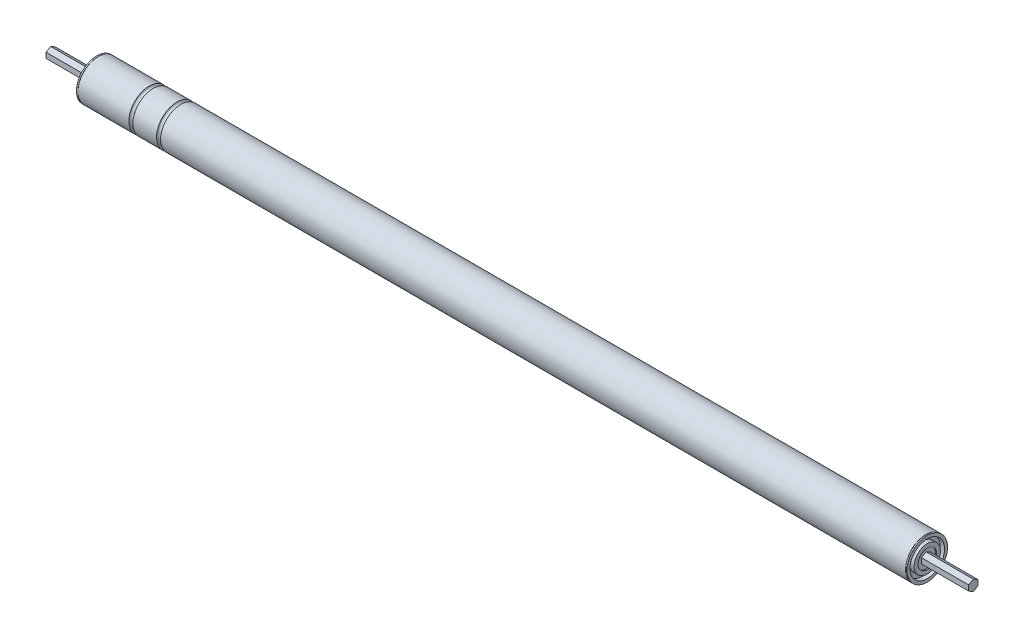
SolidWorks part; units mm, degrees
ref_plane "Front Plane" through (0, 0, 0) normal (0, 0, 1) x (1, 0, 0)
ref_plane "Top Plane" through (0, 0, 0) normal (0, 1, 0) x (1, 0, 0)
ref_plane "Right Plane" through (0, 0, 0) normal (1, 0, 0) x (0, 0, -1)
sketch "Sketch1" plane through (0, 0, 0) normal (0, 0, 1) x (1, 0, 0)
  line L0 (-493.7125, 0) -> (493.7125, 0) construction
  line L1 (493.7125, 0) -> (508, 0) construction
  line L2 (-493.7125, 0) -> (-508, 0) construction
  line L3 (0, 24.13) -> (0, -24.13) construction
  line L4 (-508, 5.5562) -> (-508, -5.5563) construction
  line L5 (508, 5.5562) -> (508, -5.5562) construction
  line L6 (-495.0969, 24.13) -> (-495.0969, -24.13) construction
  line L7 (-495.0969, 0) -> (495.0969, 0) construction
  line L8 (495.0969, 24.13) -> (495.0969, -24.13) construction
  line L9 (-430.2125, 24.13) -> (-430.2125, -24.13) construction
  line L10 (-432.5937, 21.7188) -> (-427.8312, 21.7188) construction
  line L11 (-495.3, 11.1125) -> (-495.3, -11.1125) construction
  line L12 (495.3, 11.1125) -> (495.3, -11.1125) construction
  point P2 (-495.3, 0)
  point P6 (495.3, 0)
  point P23 (-430.2125, 21.7188)
  dimension "D1" = 1.5875
  dimension "D2" = 1.5875
  dimension "BF" = 990.6
  dimension "Overall Width" = 1016
  dimension "D4" = 48.26
  dimension "D5" = 11.1125
  dimension "D6" = 990.1937
  dimension "D8" = 2.4112
  dimension "D9" = 4.7625
  dimension "D10" = 22.225
  dimension "Bearing to Groove Width" = 63.5
sketch "Sketch2" plane through (0, 0, 0) normal (0, 0, 1) x (1, 0, 0)
  line L0 (-493.7125, 0) -> (-493.7125, 11.1125)
  line L1 (-493.7125, 11.1125) -> (-495.0969, 11.1125)
  line L2 (-495.0969, 24.13) -> (-495.0969, -24.13) construction
  line L3 (-493.7125, 0) -> (-508, 0) construction
  line L4 (-495.0969, 11.1125) -> (-495.0969, 15.7129)
  line L5 (-493.7125, 0) -> (-487.9849, 0) construction
  line L6 (-493.7125, 0) -> (-487.9849, 0)
  line L7 (-495.0969, 15.7129) -> (-489.7629, 15.7129)
  line L8 (-489.7629, 15.7129) -> (-489.7629, 20.574)
  line L9 (-495.0969, 24.13) -> (-495.0969, 20.574)
  line L10 (-495.0969, 20.574) -> (-489.7629, 20.574)
  line L11 (-495.0969, 24.13) -> (-493.3189, 24.13)
  line L12 (-493.3189, 24.13) -> (-493.3189, 22.352)
  line L13 (-493.3189, 22.352) -> (-487.9849, 22.352)
  line L14 (-487.9849, 22.352) -> (-487.9849, 0)
  line L15 (-493.7125, 0) -> (493.7125, 0) construction
  line L16 (-508, 5.5562) -> (-508, -5.5563) construction
  dimension "D3" = 22.225
  dimension "D1" = 1.778
  dimension "D2" = 1.778
  dimension "D4" = 1.778
  dimension "D5" = 31.4259
  dimension "D6" = 1.778
  dimension "D7" = 5.334
revolve "Revolve1" add sketch "Sketch2" angle 360 mid plane about L5
mirror "Mirror2" about plane through (0, 0, 0) normal (1, 0, 0) of bodies 101
sketch "Sketch3" plane through (0, 0, 0) normal (1, 0, 0) x (0, 0, -1)
  circle A0 centre (0, 0) radius 24.13
  circle A1 centre (0, 0) radius 22.352 construction
  circle A2 centre (0, 0) radius 22.352 construction
extrude "Boss-Extrude1" add sketch "Sketch3" along normal up to surface (487.9849 mm away) and the other way up to surface (487.9849 mm away) up to face at (487.9849, -22.352, 0) other way up to face at (-487.9849, -22.352, 0)
chamfer "Chamfer1" distance 0.254 angle 45 2 edges at (-493.3189, -24.13, 0) (493.3189, -24.13, 0)
sketch "Sketch6" plane through (-487.9849, 0, 0) normal (-1, 0, 0) x (0, 0, 1)
  circle A0 centre (0, 0) radius 22.352 construction
  circle A1 centre (0, 0) radius 24.13
  circle A2 centre (0, 0) radius 24.13
  circle A3 centre (0, 0) radius 22.352
  dimension "D1" = 0
extrude "Boss-Extrude3" add sketch "Sketch6" along normal up to surface and the other way up to surface up to face at (-493.3189, -23.876, 0) other way up to face at (493.3189, 23.876, 0)
sketch "Sketch4" plane through (0, 0, 0) normal (1, 0, 0) x (0, 0, -1)
  line L1 (0, 6.4158) -> (-5.5563, 3.2079)
  line L2 (-5.5563, 3.2079) -> (-5.5563, -3.2079)
  line L3 (-5.5563, -3.2079) -> (0, -6.4158)
  line L4 (0, -6.4158) -> (5.5562, -3.2079)
  line L5 (5.5562, -3.2079) -> (5.5562, 3.2079)
  line L6 (5.5562, 3.2079) -> (0, 6.4158)
  circle A0 centre (0, 0) radius 5.5563 construction
  point P1 (5.5562, -3.2079)
  point P10 (5.5562, 0)
  dimension "D1" = 11.1125
extrude "Boss-Extrude2" add sketch "Sketch4" along normal up to vertex and the other way up to vertex up to point (508, 0, 0) other way up to point (-508, 0, 0)
sketch "Sketch5" plane through (0, 0, 0) normal (0, 0, 1) x (1, 0, 0)
  line L0 (-432.5937, 21.7188) -> (-427.8312, 21.7188) construction
  line L1 (-430.2125, 24.13) -> (-430.2125, -24.13) construction
  line L2 (-432.5937, 21.7188) -> (-432.5937, 25.5224) construction
  line L3 (-508, 0) -> (-493.7125, 0) construction
  line L7 (-430.2125, 24.1) -> (-432.5937, 24.1) construction
  line L8 (-433.3811, 24.8874) -> (-433.3811, 25.5224)
  line L9 (-433.3811, 25.5224) -> (-427.0439, 25.5224)
  line L10 (-427.0439, 24.8874) -> (-427.0439, 25.5224)
  arc A0 (-432.5937, 24.1) -> (-427.8313, 24.1) centre (-430.2125, 24.1) ccw
  arc A1 (-427.8313, 24.1) -> (-427.0439, 24.8874) centre (-427.0439, 24.1) cw
  arc A2 (-432.5937, 24.1) -> (-433.3811, 24.8874) centre (-433.3811, 24.1) ccw
  dimension "D2" = 0.7874
  dimension "D1" = 0.03
  dimension "D3" = 0.635
revolve "Cut-Revolve1" cut sketch "Sketch5" angle 360 mid plane about L3
pattern_linear "LPattern1" count 2 spacing 33.02 along (1, 0, 0) of "Cut-Revolve1"
ref_axis "Center Axis 1" through (307.34, 0, 0) along (-1, 0, 0)
ref_plane "Contact Plane 1" through (-508, 0, 0) normal (-1, 0, 0) x (0, 0, 1)
ref_plane "Contact Plane 2" through (-493.7125, 0, 0) normal (-1, 0, 0) x (0, 0, 1)
extrude "Boss-Extrude4" add sketch "Sketch4<2>" along normal blind 550
sketch "Sketch4<2>" plane through (0, 0, 0) normal (1, 0, 0) x (0, 0, -1) same geometry as "Sketch4"
extrude "Boss-Extrude5" add sketch "Sketch4<3>" against normal blind 550
sketch "Sketch4<3>" plane through (0, 0, 0) normal (1, 0, 0) x (0, 0, -1) same geometry as "Sketch4"
equation "\"D6@Sketch1\" = \"BF@Sketch1\"-.40625"
equation "\"D3@Sketch2\" = \"D5@Sketch1\"*2"
equation "\"D10@Sketch1\" = \"D3@Sketch2\""
equation "\"D2@Sketch2\" = \"D1@Sketch2\""
equation "\"D4@Sketch2\" = \"D2@Sketch2\""
equation "\"D6@Sketch2\" = \"D1@Sketch2\""
equation "\"D7@Sketch2\" = \"D1@Sketch2\"*3"
equation "\"D8@Sketch1\"=(\"D9@Sketch1\"/2)+.030"
